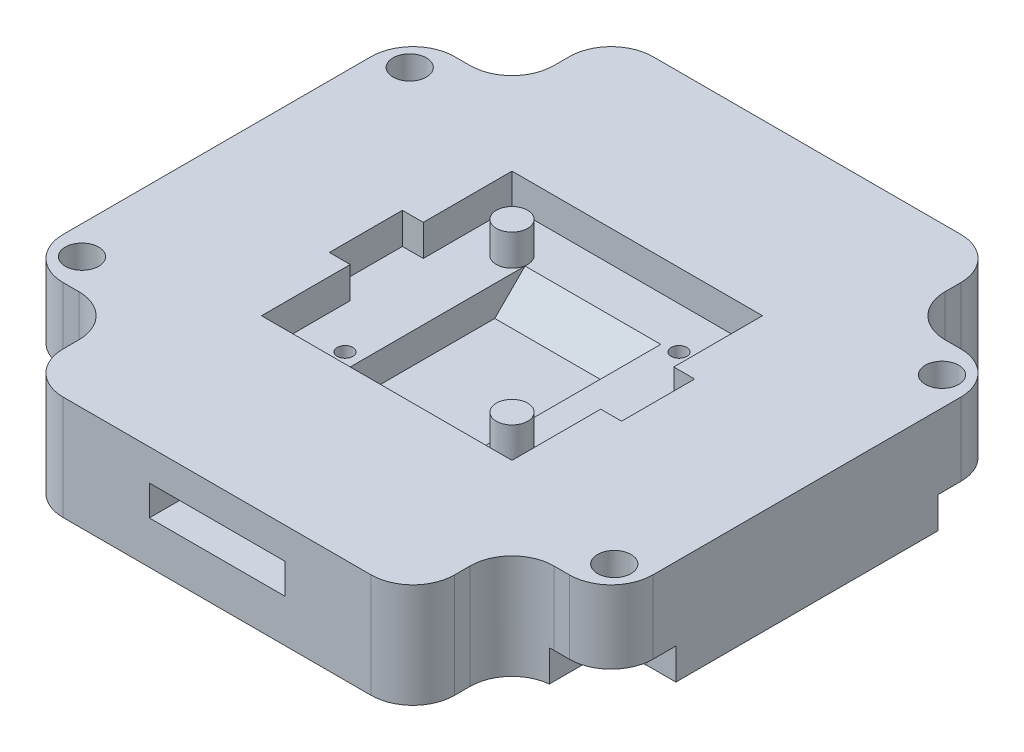
SolidWorks part; units mm, degrees
ref_plane "Ebene vorne" through (0, 0, 0) normal (0, 0, 1) x (1, 0, 0)
ref_plane "Ebene oben" through (0, 0, 0) normal (0, 1, 0) x (1, 0, 0)
ref_plane "Ebene rechts" through (0, 0, 0) normal (1, 0, 0) x (0, 0, -1)
sketch "Skizze1" plane through (0, 0, 0) normal (0, 1, 0) x (1, 0, 0)
  line L0 (18.75, 18.75) -> (28.25, 18.75)
  line L1 (-28.25, 18.75) -> (-18.75, 18.75)
  line L2 (-28.25, 18.75) -> (-28.25, -18.75)
  line L3 (-28.25, -18.75) -> (-18.75, -18.75)
  line L4 (28.25, 18.75) -> (28.25, -18.75)
  line L5 (-28.25, 18.75) -> (28.25, -18.75) construction
  line L6 (-28.25, -18.75) -> (28.25, 18.75) construction
  line L7 (-18.75, -28.25) -> (18.75, -28.25)
  line L8 (-18.75, -28.25) -> (-18.75, -18.75)
  line L9 (-18.75, 28.25) -> (18.75, 28.25)
  line L10 (18.75, -28.25) -> (18.75, -18.75)
  line L11 (-18.75, -28.25) -> (18.75, 28.25) construction
  line L12 (-18.75, 28.25) -> (18.75, -28.25) construction
  line L13 (18.75, 18.75) -> (18.75, 28.25)
  line L14 (18.75, -18.75) -> (28.25, -18.75)
  line L15 (-18.75, 18.75) -> (-18.75, 28.25)
  point P0 (0, 0)
  point P6 (0, 0)
  dimension "D1" = 56.5
  dimension "D2" = 56.5
  dimension "D3" = 37.5
extrude "Aufsatz-Linear austragen1" add sketch "Skizze1" along normal blind 10
sketch "Skizze2" plane through (0, 10, 0) normal (0, 1, 0) x (1, 0, 0)
  line L1 (-12, 12) -> (12, 12)
  line L2 (-12, 12) -> (-12, -12)
  line L3 (-12, -12) -> (12, -12)
  line L4 (12, 12) -> (12, -12)
  line L5 (-12, 12) -> (12, -12) construction
  line L6 (-12, -12) -> (12, 12) construction
  point P0 (0, 0)
  dimension "D1" = 24
extrude "Schnitt-Linear austragen1" cut sketch "Skizze2" against normal blind 3
fillet "Verrundung1" radius 4 12 edges at (-28.25, 5, 18.75) (-18.75, 5, 28.25) (-28.25, 5, -18.75) (-18.75, 5, -28.25) (18.75, 5, -28.25) (28.25, 5, -18.75) (28.25, 5, 18.75) (18.75, 5, 28.25) (18.75, 5, 18.75) (-18.75, 5, 18.75) (-18.75, 5, -18.75) (18.75, 5, -18.75)
sketch "Skizze3" plane through (0, 7, 0) normal (0, 1, 0) x (1, 0, 0)
  line L1 (-8, -8) -> (8, -8) construction
  line L2 (-8, -8) -> (-8, 8) construction
  line L3 (-8, 8) -> (8, 8) construction
  line L4 (8, -8) -> (8, 8) construction
  line L5 (-8, -8) -> (8, 8) construction
  line L6 (-8, 8) -> (8, -8) construction
  circle A0 centre (-8, 8) radius 1.5
  circle A2 centre (8, -8) radius 1.5
  point P0 (0, 0)
  dimension "D2" = 3
  dimension "D1" = 16
extrude "Aufsatz-Linear austragen2" add sketch "Skizze3" along normal blind 3
sketch "Skizze4" plane through (0, 10, 0) normal (0, 1, 0) x (1, 0, 0)
  line L0 (0, 0) -> (-50000, 0) construction
  line L1 (12, 3.5) -> (14, 3.5)
  line L2 (12, -12) -> (12, 12) construction
  line L3 (14, 3.5) -> (14, -3.5)
  line L4 (14, -3.5) -> (12, -3.5)
  line L5 (12, -3.5) -> (12, 3.5)
  dimension "D1" = 2
  dimension "D2" = 7
extrude "Schnitt-Linear austragen2" cut sketch "Skizze4" against normal blind 3
mirror "Spiegeln1" about plane through (0, 0, 0) normal (1, 0, 0) of "Schnitt-Linear austragen2"
sketch "Skizze5" plane through (0, 0, 28.25) normal (0, 0, 1) x (1, 0, 0)
  line L0 (0, 0) -> (0, -50000) construction
  line L2 (-14.75, 0) -> (14.75, 0) construction
  line L3 (-6.5, 7) -> (6.5, 7)
  line L4 (-6.5, 7) -> (-6.5, 4.1)
  line L5 (-6.5, 4.1) -> (6.5, 4.1)
  line L6 (6.5, 7) -> (6.5, 4.1)
  line L7 (-6.5, 7) -> (6.5, 4.1) construction
  line L8 (-6.5, 4.1) -> (6.5, 7) construction
  point P3 (0, 5.55)
  dimension "D1" = 2.9
  dimension "D2" = 13
  dimension "D3" = 4.1
extrude "Schnitt-Linear austragen3" cut sketch "Skizze5" against normal blind 32
chamfer "Fase1" distance 4 angle 45 1 edges at (0, 7, -3.75)
hole_wizard "Ø3.2 (3.2) Durchmesser Bohrung1" positions "Skizze8" profile "Skizze9" hole size "Ø3.2" standard "ISO"
sketch "Skizze8" plane through (0, 10, 0) normal (0, 1, 0) x (1, 0, 0)
  line L1 (25.5, 15.7) -> (-25.5, 15.7) construction
  line L2 (25.5, 15.7) -> (25.5, -15.7) construction
  line L3 (25.5, -15.7) -> (-25.5, -15.7) construction
  line L4 (-25.5, 15.7) -> (-25.5, -15.7) construction
  line L5 (25.5, 15.7) -> (-25.5, -15.7) construction
  line L6 (25.5, -15.7) -> (-25.5, 15.7) construction
  point P2 (-25.5, -15.7)
  point P195 (25.5, 15.7)
  point P196 (25.5, -15.7)
  point P197 (-25.5, 15.7)
  dimension "D1" = 51
  dimension "D2" = 31.4
sketch "Skizze9" plane through (-25.5, 10, 15.7) normal (1, 0, 0) x (0, 0, 1)
  line L0 (0, 0) -> (0, 11.9614)
  line L1 (0, 11.9614) -> (1.6, 11)
  line L2 (1.6, 11) -> (1.6, 0)
  line L5 (1.6, 0) -> (0, 0)
  line L10 (0, 11.9614) -> (-1.6, 11) construction
  line L11 (0, -6.35) -> (0, 107.95) construction
  dimension "Bohrerdurchmesser" = 3.2
  dimension "Bohrungstiefe" = 11
  dimension "Spitzenwinkel" = 118
hole_wizard "Ø1.5 (1.5) Durchmesser Bohrung1" positions "Skizze10" profile "Skizze11" hole size "Ø1.5" standard "ISO"
sketch "Skizze10" plane through (0, 7, 0) normal (0, 1, 0) x (1, 0, 0)
  line L1 (-8, 8) -> (8, 8)
  line L2 (-8, 8) -> (-8, -8)
  line L3 (-8, -8) -> (8, -8)
  line L4 (8, 8) -> (8, -8)
  line L5 (-8, 8) -> (8, -8) construction
  line L6 (-8, -8) -> (8, 8) construction
  point P456 (-8, -8)
  point P457 (8, 8)
sketch "Skizze11" plane through (8, 7, -8) normal (1, 0, 0) x (0, 0, 1)
  line L0 (0, 0) -> (0, 5.4506)
  line L1 (0, 5.4506) -> (0.75, 5)
  line L2 (0.75, 5) -> (0.75, 0)
  line L5 (0.75, 0) -> (0, 0)
  line L10 (0, 5.4506) -> (-0.75, 5) construction
  line L11 (0, -6.35) -> (0, 107.95) construction
  dimension "Bohrerdurchmesser" = 1.5
  dimension "Bohrungstiefe" = 5
  dimension "Spitzenwinkel" = 118
sketch "Skizze12" plane through (0, 0, 0) normal (0, -1, 0) x (1, 0, 0)
  line L0 (-22.35, 15.7) -> (-22.35, 18.85)
  line L1 (-25.5, 18.85) -> (-22.35, 18.85)
  line L2 (-25.5, 12.55) -> (-28.65, 12.55)
  line L3 (-28.65, 12.55) -> (-28.65, 15.7)
  arc A0 (-25.5, 12.55) -> (-22.35, 15.7) centre (-25.5, 15.7) ccw
  arc A1 (-25.5, 18.85) -> (-28.65, 15.7) centre (-25.5, 15.7) ccw
  dimension "D1" = 6.3
extrude "Schnitt-Linear austragen4" cut sketch "Skizze12" against normal blind 3
mirror "Spiegeln2" about plane through (0, 0, 0) normal (1, 0, 0) of "Schnitt-Linear austragen4"
mirror "Spiegeln3" about plane through (0, 0, 0) normal (0, 0, 1) of "Spiegeln2"
